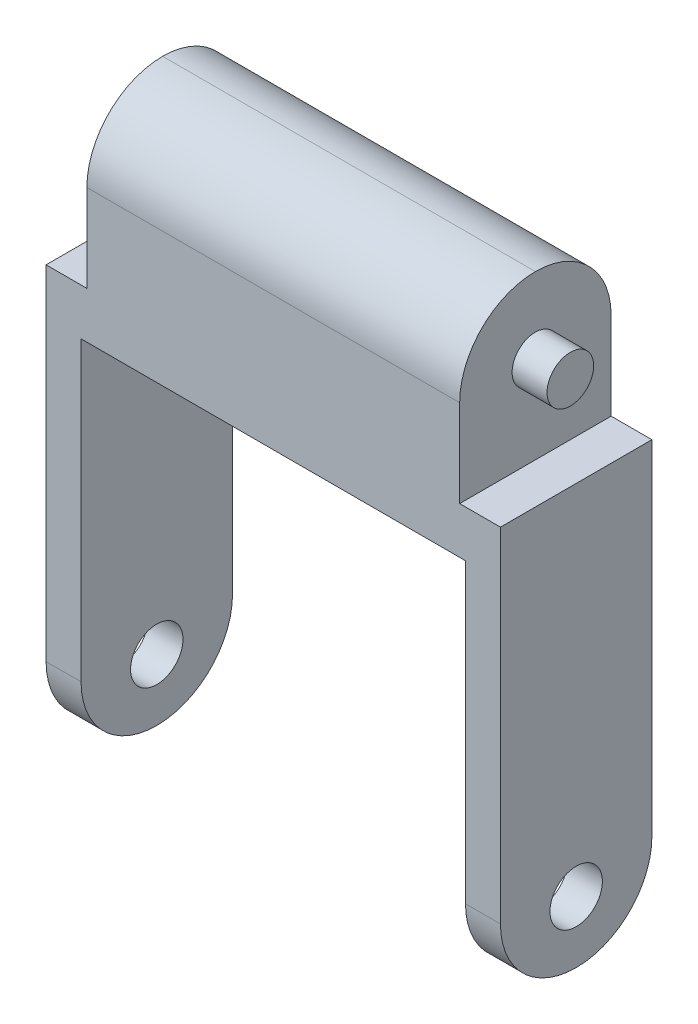
SolidWorks part; units mm, degrees
ref_plane "Plano frontal" through (0, 0, 0) normal (0, 0, 1) x (1, 0, 0)
ref_plane "Plano superior" through (0, 0, 0) normal (0, 1, 0) x (1, 0, 0)
ref_plane "Plano direito" through (0, 0, 0) normal (1, 0, 0) x (0, 0, -1)
sketch "Sketch1" plane through (0, 0, 0) normal (0, 0, 1) x (1, 0, 0)
  line L0 (3, 0) -> (3, 32)
  line L1 (0, 0) -> (3, 0)
  line L2 (0, 0) -> (0, 36)
  line L3 (3.5, 50) -> (35.5, 50)
  line L4 (39, 0) -> (39, 36)
  line L5 (3, 32) -> (36, 32)
  line L6 (36, 32) -> (36, 0)
  line L7 (36, 0) -> (39, 0)
  line L8 (0, 36) -> (3.5, 36)
  line L9 (3.5, 36) -> (3.5, 50)
  line L10 (35.5, 50) -> (35.5, 36)
  line L11 (35.5, 36) -> (39, 36)
  dimension "D1" = 39
  dimension "D2" = 50
  dimension "D3" = 3
  dimension "D4" = 3
  dimension "D5" = 18
  dimension "D6" = 14
  dimension "D7" = 14
  dimension "D8" = 3.5
  dimension "D9" = 32
extrude "Boss-Extrude1" add sketch "Sketch1" along normal blind 13
sketch "Sketch2" plane through (0, 0, 0) normal (-1, 0, 0) x (0, 0, 1)
  circle A0 centre (6.5, 5.294) radius 2.25
  dimension "D1" = 4.5
extrude "Cut-Extrude1" cut sketch "Sketch2" against normal through all
sketch "Sketch3" plane through (3.5, 0, 0) normal (-1, 0, 0) x (0, 0, 1)
  line L0 (13, 50) -> (0, 50) construction
  circle A0 centre (6.5, 43.5) radius 2
  dimension "D1" = 4
  dimension "D2" = 6.5
extrude "Boss-Extrude2" add sketch "Sketch3" along normal blind 3
sketch "Sketch4" plane through (35.5, 0, 0) normal (1, 0, 0) x (0, 0, -1)
  line L0 (-13, 50) -> (0, 50) construction
  circle A0 centre (-6.5, 43.5) radius 2
  dimension "D1" = 4
  dimension "D2" = 6.5
extrude "Boss-Extrude3" add sketch "Sketch4" along normal blind 3
fillet "Fillet1" radius 6.5 4 edges at (1.5, 0, 0) (1.5, 0, 13) (37.5, 0, 0) (37.5, 0, 13)
fillet "Fillet2" radius 6.5 2 edges at (19.5, 50, 13) (19.5, 50, 0)
